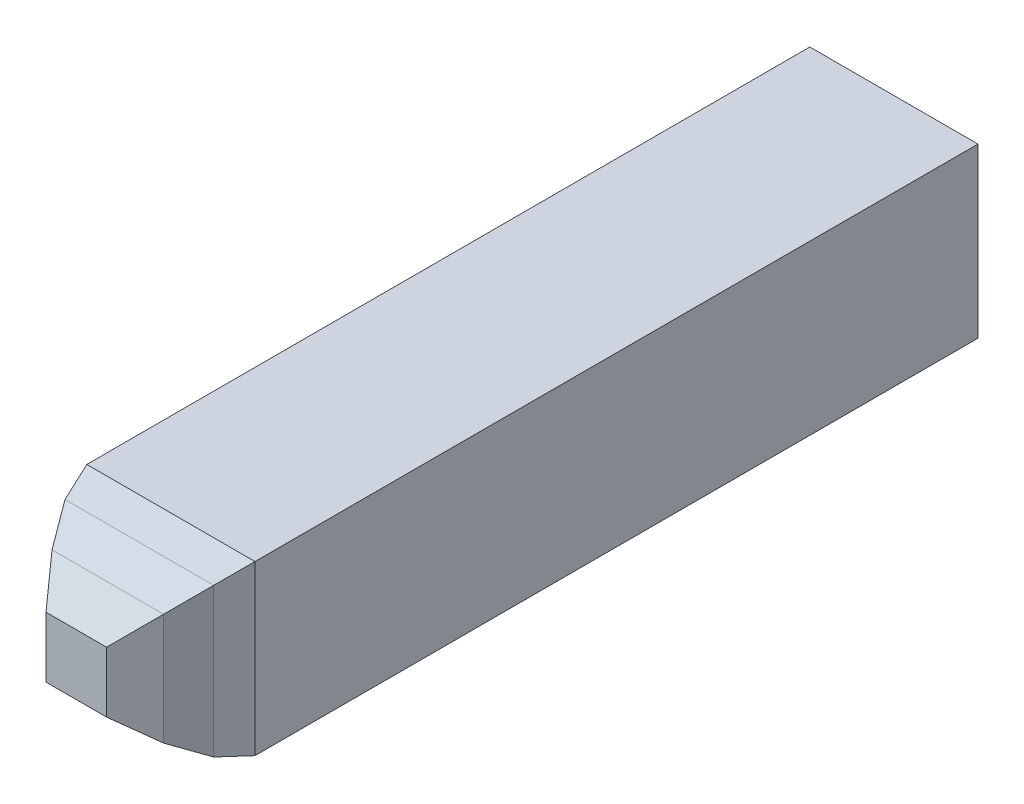
SolidWorks part; units mm, degrees
ref_plane "Front Plane" through (0, 0, 0) normal (0, 0, 1) x (1, 0, 0)
ref_plane "Top Plane" through (0, 0, 0) normal (0, 1, 0) x (1, 0, 0)
ref_plane "Right Plane" through (0, 0, 0) normal (1, 0, 0) x (0, 0, -1)
sketch "Sketch1" plane through (0, 0, 0) normal (0, 0, 1) x (1, 0, 0)
  line L1 (-50.8, -50.8) -> (50.8, -50.8)
  line L2 (-50.8, -50.8) -> (-50.8, 50.8)
  line L3 (-50.8, 50.8) -> (50.8, 50.8)
  line L4 (50.8, -50.8) -> (50.8, 50.8)
  line L5 (-50.8, -50.8) -> (50.8, 50.8) construction
  line L6 (-50.8, 50.8) -> (50.8, -50.8) construction
  point P0 (0, 0)
  dimension "D1" = 101.6
  dimension "D2" = 101.6
extrude "Boss-Extrude1" add sketch "Sketch1" along normal blind 436.88 contours L2 L1 L4 L3
ref_plane "Plane1" through (0, 0, 455.93) normal (0, 0, 1) x (1, 0, 0)
sketch "Sketch3" plane through (0, 0, 455.93) normal (0, 0, 1) x (1, 0, 0)
  line L1 (-44.9132, -44.9132) -> (44.9132, -44.9132)
  line L2 (-44.9132, -44.9132) -> (-44.9132, 44.9132)
  line L3 (-44.9132, 44.9132) -> (44.9132, 44.9132)
  line L4 (44.9132, -44.9132) -> (44.9132, 44.9132)
  line L5 (-44.9132, -44.9132) -> (44.9132, 44.9132) construction
  line L6 (-44.9132, 44.9132) -> (44.9132, -44.9132) construction
  point P0 (0, 0)
  dimension "D1" = 89.8265
  dimension "D2" = 89.8265
sketch "Sketch5" plane through (0, 0, 436.88) normal (0, 0, 1) x (1, 0, 0)
  line L0 (50.8, -50.8) -> (50.8, 50.8) construction
  line L1 (-50.8, 50.8) -> (50.8, 50.8) construction
  line L2 (-50.8, -50.8) -> (-50.8, 50.8) construction
  line L3 (-50.8, -50.8) -> (50.8, -50.8) construction
  line L4 (50.8, -50.8) -> (50.8, 50.8)
  line L5 (-50.8, 50.8) -> (50.8, 50.8)
  line L6 (-50.8, -50.8) -> (-50.8, 50.8)
  line L7 (-50.8, -50.8) -> (50.8, -50.8)
loft "Loft2" add profiles "Sketch5", "Sketch3" connector at (-50.8, 50.8, 436.88) connector at (-44.9132, 44.9132, 455.93)
ref_plane "Plane2" through (0, 0, 474.98) normal (0, 0, 1) x (1, 0, 0)
sketch "Sketch6" plane through (0, 0, 474.98) normal (0, 0, 1) x (1, 0, 0)
  line L1 (-33.7159, -33.7159) -> (33.7159, -33.7159)
  line L2 (-33.7159, -33.7159) -> (-33.7159, 33.7159)
  line L3 (-33.7159, 33.7159) -> (33.7159, 33.7159)
  line L4 (33.7159, -33.7159) -> (33.7159, 33.7159)
  line L5 (-33.7159, -33.7159) -> (33.7159, 33.7159) construction
  line L6 (-33.7159, 33.7159) -> (33.7159, -33.7159) construction
  point P0 (0, 0)
  dimension "D1" = 67.4318
  dimension "D2" = 67.4318
loft "Loft3" add profiles "Sketch3<6>", "Sketch6" connector at (-44.9132, 44.9132, 455.93) connector at (-33.7159, 33.7159, 474.98)
sketch "Sketch3<6>" plane through (0, 0, 455.93) normal (0, 0, 1) x (1, 0, 0) same geometry as "Sketch3"
ref_plane "Plane3" through (0, 0, 494.03) normal (0, 0, 1) x (1, 0, 0)
sketch "Sketch7" plane through (0, 0, 494.03) normal (0, 0, 1) x (1, 0, 0)
  line L5 (-44.9132, -44.9132) -> (44.9132, 44.9132) construction
  line L6 (-18.3041, -18.3041) -> (18.3041, -18.3041)
  line L8 (-18.3041, -18.3041) -> (-18.3041, 18.3041)
  line L9 (-18.3041, 18.3041) -> (18.3041, 18.3041)
  line L10 (18.3041, -18.3041) -> (18.3041, 18.3041)
  line L11 (-18.3041, -18.3041) -> (18.3041, 18.3041) construction
  line L12 (-18.3041, 18.3041) -> (18.3041, -18.3041) construction
  point P1 (0, 0)
  dimension "D1" = 36.6083
  dimension "D2" = 36.6083
loft "Loft4" add profiles "Sketch6<4>", "Sketch7" connector at (33.7159, 33.7159, 474.98) connector at (18.3041, 18.3041, 494.03)
sketch "Sketch6<4>" plane through (0, 0, 474.98) normal (0, 0, 1) x (1, 0, 0) same geometry as "Sketch6"
ref_axis "Axis1" through (0, 0, 494.03) along (0, 0, 1)
ref_plane "Plane5" through (0, 0, 0) normal (-0.7071, 0.7071, 0) x (0.7071, 0.7071, 0)
sketch "Sketch9" plane through (0, 0, 0) normal (-0.7071, 0.7071, 0) x (0.7071, 0.7071, 0)
  line L0 (-25.886, -494.03) -> (0, -494.03) construction
  line L1 (0, -494.03) -> (25.886, -494.03) construction
  line L2 (-25.886, -494.03) -> (0, -494.03)
  line L3 (0, -494.03) -> (25.886, -494.03)
  line L4 (0, -494.03) -> (0, -513.08)
  line L5 (0, -494.03) -> (0, -511.1148) construction
  line L6 (0, -513.08) -> (25.886, -494.03)
  point P2 (0, 0)
  point P8 (0, 0)
  dimension "D1" = 19.05
ref_point "Point1"
